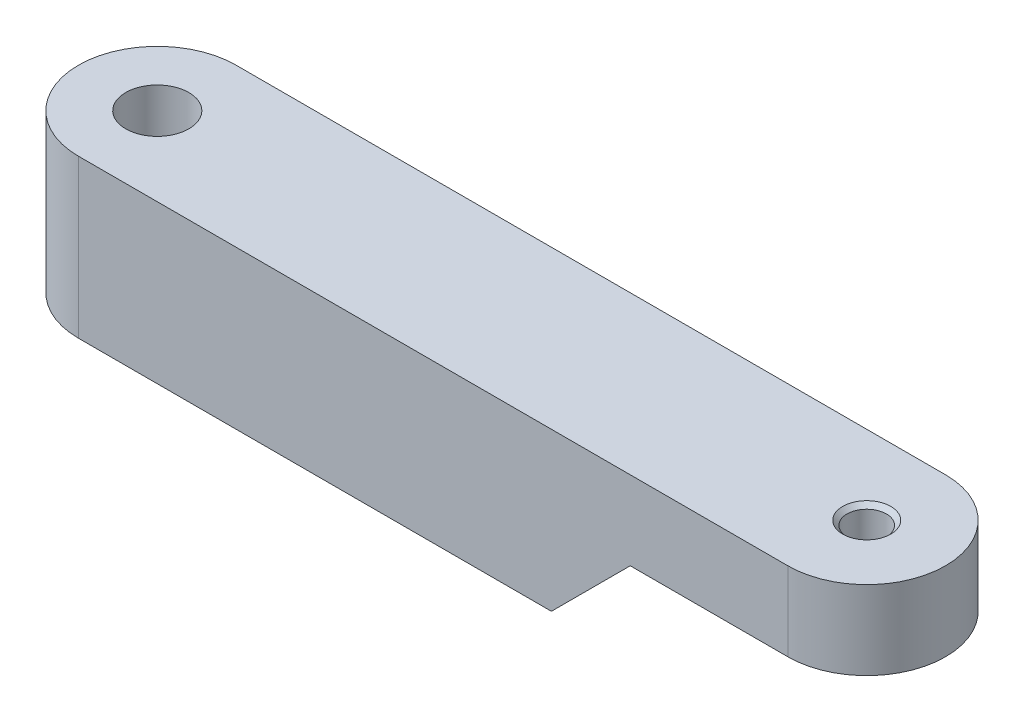
SolidWorks part; units mm, degrees
ref_plane "Plan de face" through (0, 0, 0) normal (0, 0, 1) x (1, 0, 0)
ref_plane "Plan de dessus" through (0, 0, 0) normal (0, 1, 0) x (1, 0, 0)
ref_plane "Plan de droite" through (0, 0, 0) normal (1, 0, 0) x (0, 0, -1)
sketch "Esquisse1" plane through (0, 0, 0) normal (0, 1, 0) x (1, 0, 0)
  line L1 (0, 5) -> (45, 5)
  line L3 (0, -5) -> (45, -5)
  circle A0 centre (0, 0) radius 2
  arc A1 (45, 5) -> (45, -5) centre (45, 0) cw
  arc A2 (0, 5) -> (0, -5) centre (0, 0) ccw
  dimension "D3" = 4
  dimension "D1" = 10
  dimension "D2" = 45
extrude "Boss.-Extru.1" add sketch "Esquisse1" along normal mid plane 10
hole_wizard "Trou taraudé M3x0.51" positions "Esquisse3" profile "Esquisse2" tap size "M3x0.5" standard "Ansi Metric" end condition through all
sketch "Esquisse3" plane through (0, 5, 0) normal (0, 1, 0) x (1, 0, 0)
  arc A0 (45, -5) -> (45, 5) centre (45, 0) ccw construction
  point P0 (45, 0)
sketch "Esquisse2" plane through (45, 5, 0) normal (1, 0, 0) x (0, 0, 1)
  line L0 (0, 0) -> (0, 10)
  line L1 (0, 10) -> (1.25, 10)
  line L2 (1.25, 10) -> (1.25, 0.275)
  line L3 (1.25, 0.275) -> (1.525, 0)
  line L5 (1.525, 0) -> (0, 0)
  line L6 (-1.25, 0.275) -> (-1.525, 0) construction
  line L11 (0, -6.35) -> (0, 107.95) construction
  dimension "Diamètre du trou pour taraudage jusqu'au prochain" = 2.5
  dimension "Profondeur du trou pour taraudage jusqu'au prochain" = 10
  dimension "Diamètre du fraisage entrant" = 3.05
  dimension "Angle du fraisage entrant" = 90
cosmetic thread "Filetage de perçage1" parameters "D2"=3
sketch "Esquisse4" plane through (0, 0, 0) normal (0, 0, 1) x (1, 0, 0)
  line L1 (35, 0) -> (50, 0)
  line L2 (35, 0) -> (30, -5)
  line L3 (30, -5) -> (50, -5)
  line L4 (50, 0) -> (50, -5)
  line L5 (50, -5) -> (50, 5) construction
  line L7 (0, -5) -> (45, -5) construction
  dimension "D1" = 45
  dimension "D3" = 5
  dimension "D4" = 15
extrude "Enlèv. mat.-Extru.1" cut sketch "Esquisse4" against normal through all and the other way through all
